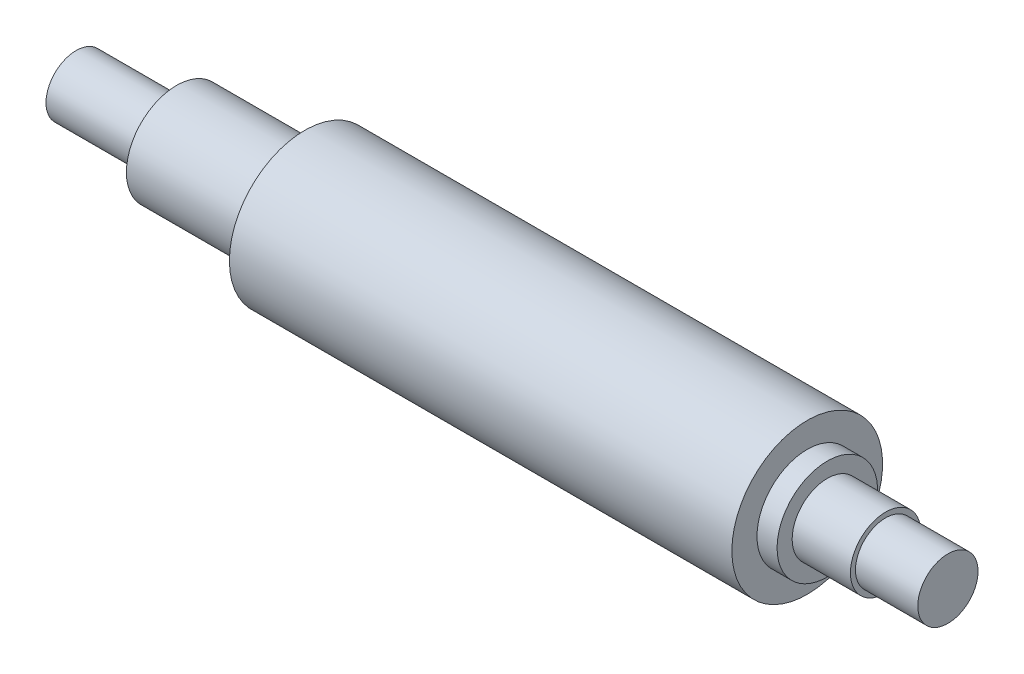
SolidWorks part; units mm, degrees
material "Alloy Steel"
ref_plane "Front Plane" through (0, 0, 0) normal (0, 0, 1) x (1, 0, 0)
ref_plane "Top Plane" through (0, 0, 0) normal (0, 1, 0) x (1, 0, 0)
ref_plane "Right Plane" through (0, 0, 0) normal (1, 0, 0) x (0, 0, -1)
sketch "Sketch2" plane through (0, 0, 0) normal (0, 0, 1) x (1, 0, 0)
  line L0 (-40.875, 0) -> (40.875, 0)
  line L1 (-40.875, 0) -> (-40.875, 3)
  line L2 (-40.875, 3) -> (-30.875, 3)
  line L3 (-13.125, 5) -> (-13.125, 6)
  line L4 (-13.125, 6) -> (26.875, 6)
  line L5 (26.875, 6) -> (26.875, 5)
  line L6 (-30.875, 3) -> (-30.875, 5)
  line L7 (-30.875, 5) -> (-13.125, 5)
  line L8 (26.875, 5) -> (28.875, 5)
  line L9 (28.875, 5) -> (28.875, 3.5)
  line L10 (28.875, 3.5) -> (34.675, 3.5)
  line L11 (34.675, 3.5) -> (34.675, 3)
  line L13 (34.675, 3) -> (40.875, 3)
  line L14 (40.875, 3) -> (40.875, 0)
  point P5 (0, 0)
  dimension "D2" = 6
  dimension "D3" = 3
  dimension "D4" = 10
  dimension "D5" = 27.75
  dimension "D6" = 40
  dimension "D7" = 5.8
  dimension "D8" = 2
  dimension "D9" = 5
  dimension "D11" = 5
  dimension "D12" = 6.2
  dimension "D10" = 3.5
  dimension "D13" = 3
revolve "Revolve1" [suppressed] add sketch "Sketch2" angle 360 about L0
sketch "Sketch3" plane through (0, 0, 0) normal (0, 0, 1) x (1, 0, 0)
  line L0 (-43.375, 0) -> (43.375, 0)
  line L1 (-43.375, 0) -> (-43.375, 3)
  line L2 (-43.375, 3) -> (-33.375, 3)
  line L3 (-20.625, 5) -> (-20.625, 7.5)
  line L4 (-20.625, 7.5) -> (29.375, 7.5)
  line L5 (29.375, 7.5) -> (29.375, 5)
  line L6 (-33.375, 3) -> (-33.375, 5)
  line L7 (-33.375, 5) -> (-20.625, 5)
  line L8 (29.375, 5) -> (31.375, 5)
  line L9 (31.375, 5) -> (31.375, 3.5)
  line L10 (31.375, 3.5) -> (37.175, 3.5)
  line L11 (43.375, 3) -> (43.375, 0)
  line L13 (4.375, 7.5) -> (4.375, 16.7852) construction
  line L14 (37.175, 3.5) -> (37.175, 3)
  line L15 (37.175, 3) -> (43.375, 3)
  point P4 (0, 0)
  point P17 (29.375, 6.25)
  dimension "D12" = 6.2
  dimension "D2" = 7.5
  dimension "D4" = 3
  dimension "D1" = 10
  dimension "D8" = 5
  dimension "D10" = 5
  dimension "D3" = 50
  dimension "D5" = 22.75
  dimension "D7" = 2
  dimension "D6" = 3.5
  dimension "D9" = 3
  dimension "D11" = 5.8
revolve "Revolve2" add sketch "Sketch3" angle 360 about L0
equation "\"mini-flipper-shaft-diameter\"= 26mm"
equation "\"mini-shaft-ring-groove-diam\"= 7.8mm"
equation "\"mini-shaft-ring-groove-width\"= 1mm"
equation "\"dtCoverPlate-DistFrom-GearCent\"= 73mm"
equation "\"wormGearShaft-L\"= \"dtCoverPlate-DistFrom-GearCent\" - 27.75 + 3.75"
equation "\"wormGearShaft-Dsmall\"= 6mm"
equation "\"wormGearShaft-Dworm\"= 12mm"
equation "\"D3@Sketch2\"=\"wormGearShaft-Dsmall\"/2"
equation "\"D4@Sketch3\"=\"wormGearShaft-Dsmall\"/2"
equation "\"wormL-D\" = 12mm"
equation "\"wormR-D\" = 15mm"
equation "\"wormGearL-D\" = 40mm"
equation "\"wormGearR-D\" = 50mm"
equation "\"D5@Sketch3\"=73-\"wormGearR-D\"/2 - 17.25-8"
equation "\"D5@Sketch2\"=73-\"wormGearL-D\"/2 -17.25-8"
